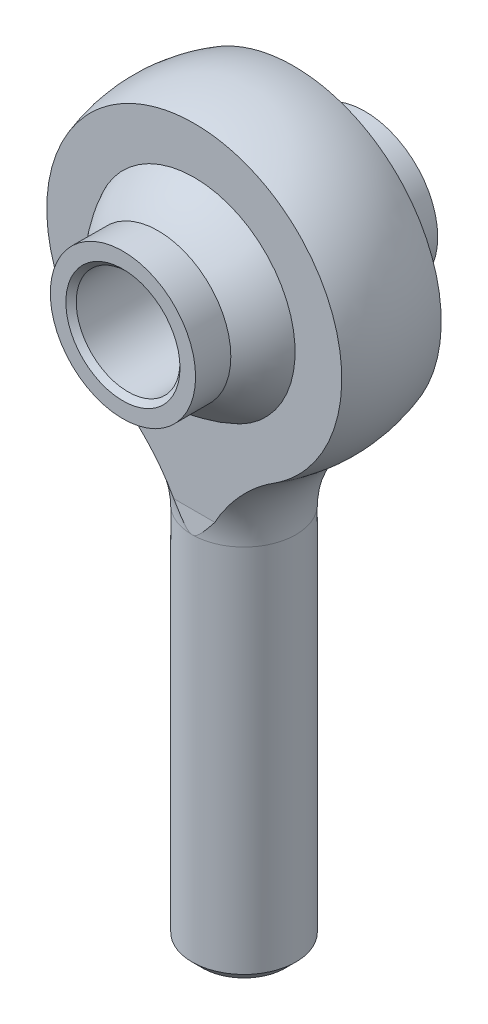
SolidWorks part; units mm, degrees
material "AISI 4130 Steel, normalized at 870C"
ref_plane "Front" through (0, 0, 0) normal (0, 0, 1) x (1, 0, 0)
ref_plane "Top" through (0, 0, 0) normal (0, 1, 0) x (1, 0, 0)
ref_plane "Right" through (0, 0, 0) normal (1, 0, 0) x (0, 0, -1)
sketch "Sketch1" plane through (0, 0, 0) normal (0, 0, 1) x (1, 0, 0)
  line L0 (0, 0) -> (0, -34.925)
  line L1 (0, -34.925) -> (4.7625, -34.925)
  line L2 (4.7625, -34.925) -> (4.7625, 0)
  line L3 (4.7625, 0) -> (0, 0)
  line L5 (0, 33.3375) -> (0, 0) construction
  line L6 (0, 33.3375) -> (14.2875, 33.3375) construction
  line L7 (14.2875, 33.3375) -> (14.2875, 19.05) construction
  line L8 (-4.7625, -34.925) -> (-4.7625, 0) construction
  line L9 (3.8092, -34.925) -> (4.7625, -33.9717)
  line L10 (4.8772, -34.8588) -> (4.8772, -35.918) construction
  line L11 (4.8772, -35.918) -> (3.9599, -35.3884) construction
  line L12 (3.9599, -35.3884) -> (4.8772, -34.8588) construction
  line L13 (3.9599, -35.3884) -> (4.0745, -35.3884) construction
  line L14 (4.8772, -35.3884) -> (4.7625, -35.3884) construction
  line L15 (4.0745, -35.4546) -> (4.0745, -35.3222) construction
  line L16 (4.7625, -35.8518) -> (4.7625, -34.925) construction
  line L17 (4.8198, -35.8849) -> (4.8198, -34.8919) construction
  arc A0 (8.5725, 7.62) -> (0, 33.3375) centre (0, 19.05) ccw construction
  circle A1 centre (0, 19.05) radius 4.7625 construction
  circle A2 centre (0, 19.05) radius 10.3187 construction
  circle A3 centre (0, 19.05) radius 10.8347 construction
  arc A4 (4.7625, 0) -> (8.5725, 7.62) centre (14.2875, 0) cw construction
  point P16 (-4.7625, -31.2179)
  point P28 (4.0745, -35.3884)
  point P31 (4.7625, -35.3884)
  point P34 (4.8198, -35.3884)
  dimension "Ball Dia" = 20.6375
  dimension "D1" = 21.6694
  dimension "ID" = 9.525
  dimension "D2" = 3.7071
  dimension "D3" = 45
  dimension "D4" = 0.9533
  dimension "Pitch" = 1.0592
  dimension "D5" = 0.1324
  dimension "Thread Size" = 9.525
  dimension "Overall Width" = 28.575
  dimension "Shank Thread Length" = 34.925
  dimension "Shank Center Length" = 53.975
sketch "Sketch2" plane through (0, 0, 0) normal (1, 0, 0) x (0, 0, -1)
  line L0 (-11.1125, 19.05) -> (11.1125, 19.05)
  line L2 (0, 25.7175) -> (0, 12.3825)
  line L3 (0, 23.8125) -> (0, 14.2875) construction
  line L4 (11.1125, 25.7175) -> (-11.1125, 25.7175)
  line L5 (11.1125, 23.8125) -> (-11.1125, 23.8125)
  line L6 (11.1125, 14.2875) -> (-11.1125, 14.2875)
  line L7 (11.1125, 12.3825) -> (-11.1125, 12.3825)
  line L8 (0, 19.05) -> (-11.1125, 24.8348) construction
  line L9 (0, 19.05) -> (-11.1125, 13.2652) construction
  point P0 (0, 23.8125)
  point P4 (0, 19.05)
  point P9 (0, 19.05)
  point P10 (0, 14.2875)
  point P18 (0, 23.8125)
  point P21 (0, 25.7175)
  point P24 (0, 14.2875)
  point P27 (0, 12.3825)
  dimension "D1" = 13.335
  dimension "Overall Thickness" = 22.225
  dimension "Maximum Ball Swivel" = 55
sketch "Sketch13" plane through (0, 0, 0) normal (0, 0, 1) x (1, 0, 0)
  line L0 (3.8092, -34.925) -> (4.7625, -33.9717) construction
  line L1 (3.8092, -34.925) -> (4.7625, -33.9717)
  line L4 (0, 0) -> (0, -34.925)
  line L5 (0, -34.925) -> (4.7625, -34.925)
  line L6 (4.7625, -34.925) -> (4.7625, 0)
  line L7 (4.7625, 0) -> (0, 0)
  line L8 (0, 0) -> (0, -34.925)
  line L9 (0, -34.925) -> (3.8092, -34.925)
  line L10 (4.7625, -33.9717) -> (4.7625, 0)
  line L11 (4.7625, 0) -> (0, 0)
  dimension "D1" = 0
revolve "Revolve4" add sketch "Sketch13" angle 360 about L8
sketch "Sketch4" plane through (0, 0, 0) normal (0, 0, 1) x (1, 0, 0)
  line L0 (4.7625, 0) -> (0, 0) construction
  line L1 (0, 8.7312) -> (0, 0)
  line L2 (0, 33.3375) -> (0, 0) construction
  line L3 (4.7625, 0) -> (0, 0)
  line L5 (0, 33.3375) -> (0, 29.3687)
  line L6 (0, 33.3375) -> (0, 35.8775) construction
  arc A0 (8.5725, 7.62) -> (0, 33.3375) centre (0, 19.05) ccw construction
  arc A1 (8.5725, 7.62) -> (0, 33.3375) centre (0, 19.05) ccw
  arc A2 (8.5725, 7.62) -> (4.7625, 0) centre (14.2875, 0) ccw construction
  arc A3 (8.5725, 7.62) -> (4.7625, 0) centre (14.2875, 0) ccw
  circle A4 centre (0, 19.05) radius 10.3187 construction
  arc A5 (0, 8.7312) -> (0, 29.3687) centre (0, 19.05) ccw
  dimension "D1" = 2.54
revolve "Revolve2" add sketch "Sketch4" angle 360 about L6
sketch "Sketch5" plane through (0, 0, 0) normal (1, 0, 0) x (0, 0, -1)
  line L0 (4.5641, 33.3375) -> (14.2875, 33.3375)
  line L1 (-4.5641, 33.3375) -> (4.5641, 33.3375) construction
  line L2 (-4.5641, 33.3375) -> (-4.5641, 1.8256)
  line L3 (-4.7625, 0) -> (4.7625, 0) construction
  line L4 (4.5641, 33.3375) -> (4.5641, 1.8256)
  line L5 (14.2875, 33.3375) -> (14.2875, 0)
  line L6 (14.2875, 0) -> (4.7625, 0)
  line L7 (-4.7625, 0) -> (-14.2875, 0)
  line L8 (-14.2875, 0) -> (-14.2875, 33.3375)
  line L9 (-14.2875, 33.3375) -> (-4.5641, 33.3375)
  line L10 (4.7625, 0) -> (4.5641, 1.8256)
  line L11 (-4.7625, 0) -> (-4.5641, 1.8256)
  line L12 (-4.5641, 1.8256) -> (4.5641, 1.8256) construction
  line L13 (0, 0) -> (0, 1.8256) construction
  arc A0 (8.5725, 7.62) -> (-8.5725, 7.62) centre (0, 19.05) ccw construction
  dimension "F" = 9.1281
  dimension "D2" = 1.8256
  dimension "D1" = 9.525
extrude "Cut-Extrude1" cut sketch "Sketch5" against normal through all and the other way through all
sketch "Sketch7" plane through (0, 0, 0) normal (0, 0, 1) x (1, 0, 0)
  line L0 (0, 29.3687) -> (0, 8.7312)
  line L1 (0, 33.3375) -> (0, 0) construction
  line L2 (0, 0) -> (0, 8.7312) construction
  arc A0 (0, 8.7312) -> (0, 29.3687) centre (0, 19.05) ccw
  circle A1 centre (0, 19.05) radius 10.3187 construction
revolve "Revolve3" add sketch "Sketch7" angle 360 about L2
sketch "Sketch10" plane through (0, 0, 0) normal (0, 0, 1) x (1, 0, 0)
  circle A0 centre (0, 19.05) radius 4.7625 construction
  circle A1 centre (0, 19.05) radius 4.7625
extrude "Cut-Extrude4" cut sketch "Sketch10" against normal through all and the other way through all
sketch "Sketch12" plane through (0, 0, 0) normal (0, 0, 1) x (1, 0, 0)
  circle A0 centre (0, 19.05) radius 6.6675
  circle A1 centre (0, 19.05) radius 4.7625 construction
  circle A2 centre (0, 19.05) radius 4.7625
  dimension "D1" = 13.335
extrude "Extrude1" add sketch "Sketch12" against normal up to vertex (11.1125 mm away) and the other way up to vertex (11.1125 mm away) up to point (0, 19.05, -11.1125) other way up to point (0, 19.05, 11.1125)
chamfer "Chamfer1" distance 0.4762 angle 45 2 edges at (4.7625, 19.05, -11.1125) (4.7625, 19.05, 11.1125)
sketch "Sketch11" plane through (0, 0, 0) normal (1, 0, 0) x (0, 0, -1)
  line L5 (0, 19.05) -> (0.0074, 19.05) construction
  line L9 (-4.5641, 32.5889) -> (-4.5641, 7.62) construction
  line L10 (4.5641, 7.62) -> (4.5641, 32.5889) construction
  arc A0 (-7.8753, 12.3825) -> (7.8753, 12.3825) centre (0, 19.05) ccw construction
  arc A1 (7.8753, 25.7175) -> (-7.8753, 25.7175) centre (0, 19.05) ccw construction
  arc A2 (-4.5641, 9.7955) -> (4.5641, 9.7955) centre (0, 19.05) ccw
  arc A3 (4.5641, 28.3045) -> (-4.5641, 28.3045) centre (0, 19.05) ccw
sketch "Sketch14" [suppressed] plane through (0, -34.925, 0) normal (0, -1, 0) x (1, 0, 0)
  circle A0 centre (0, 0) radius 4.7625
curve "Helix/Spiral1" [suppressed] pitch 1.0592 height 35.9842 turns 33.9736
split "Split1" [suppressed] bodies to split 112 118 115
sketch "Sketch15" [suppressed] plane through (0, 0, 0) normal (0, 0, 1) x (1, 0, 0)
  line L0 (4.0745, -35.3222) -> (4.8198, -34.8919)
  line L1 (4.8198, -34.8919) -> (4.8198, -35.8849)
  line L2 (4.8198, -35.8849) -> (4.0745, -35.4546)
  line L3 (4.0745, -35.4546) -> (4.0745, -35.3222)
sweep "Cut-Sweep1" [suppressed] cut profiles "Sketch15" path "Helix/Spiral1"
sketch "Sketch16" [suppressed] plane through (0, 0, 0) normal (0, 1, 0) x (1, 0, 0)
  circle A0 centre (0, 0) radius 4.7625
extrude "Boss-Extrude1" [suppressed] add sketch "Sketch16" against normal blind 2.54 draft 45
equation "\"D1@Sketch1\"=\"Ball Dia@Sketch1\"*1.05"
equation "\"D1@Chamfer1\" = \"ID@Sketch1\" / 20"
equation "\"D1@Sketch5\"= \"Thread Size@Sketch1\""
equation "\"D2@Sketch5\"=\"F@Sketch5\"/5"
equation "\"D1@Sketch12\"= \"ID@Sketch1\" * 1.4"
equation "\"D5@Sketch1\"=\"Pitch@Sketch1\"/8"
equation "\"D4@Sketch1\"=\"Pitch@Sketch1\"*.9"
equation "\"D3@Helix/Spiral1\"= \"Shank Thread Length@Sketch1\" + \"Pitch@Sketch1\""
equation "\"D4@Helix/Spiral1\"=\"Pitch@Sketch1\""
equation "\"D2@Sketch1\"=\"Pitch@Sketch1\"*3.5"
equation "\"D1@Sketch2\"=\"ID@Sketch1\"*1.4"
